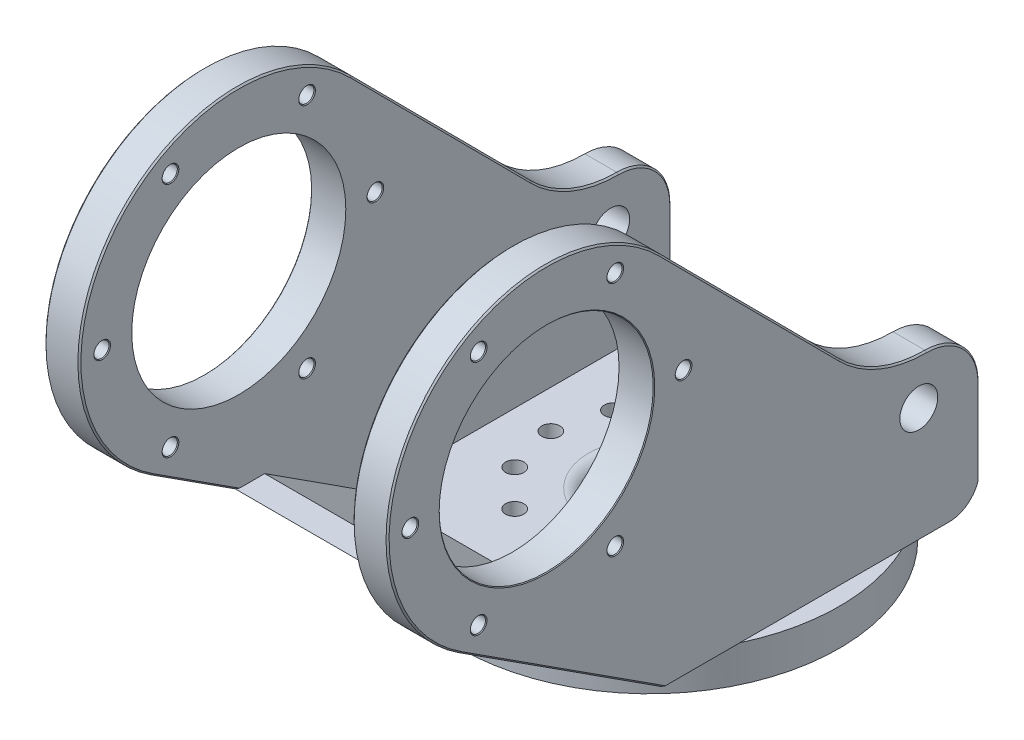
SolidWorks part; units mm, degrees
ref_plane "前视基准面" through (0, 0, 0) normal (0, 0, 1) x (1, 0, 0)
ref_plane "上视基准面" through (0, 0, 0) normal (0, 1, 0) x (1, 0, 0)
ref_plane "右视基准面" through (0, 0, 0) normal (1, 0, 0) x (0, 0, -1)
other "Configuration Table"
sketch "草图1" plane through (0, 0, 0) normal (0, 1, 0) x (1, 0, 0)
  circle A0 centre (0, 0) radius 125
  dimension "D1" = 250
extrude "凸台-拉伸1" add sketch "草图1" along normal mid plane 29
sketch "草图2" plane through (0, 0, 0) normal (1, 0, 0) x (0, 0, -1)
  line L0 (0, -14.5) -> (55, -14.5)
  line L1 (-125, -14.5) -> (125, -14.5) construction
  line L2 (55, -14.5) -> (55, -10.5)
  line L3 (55, -10.5) -> (30, -10.5)
  line L4 (30, -10.5) -> (30, 4.5)
  line L6 (125, 14.5) -> (-125, 14.5) construction
  line L7 (0, -14.5) -> (0, 14.5)
  line L8 (0, 14.5) -> (40, 14.5)
  arc A0 (30, 4.5) -> (40, 14.5) centre (40, 4.5) cw
  dimension "D3" = 10
  dimension "D1" = 55
  dimension "D2" = 30
  dimension "D4" = 4
revolve "切除-旋转1" cut sketch "草图2" angle 360 about L7
sketch "草图3" plane through (0, 14.5, 0) normal (0, 1, 0) x (1, 0, 0)
  circle A0 centre (0, 0) radius 65 construction
  circle A1 centre (0, 65) radius 6
  circle A2 centre (32.5, 56.2917) radius 6
  circle A3 centre (56.2917, 32.5) radius 6
  circle A4 centre (65, 0) radius 6
  circle A5 centre (56.2917, -32.5) radius 6
  circle A6 centre (32.5, -56.2917) radius 6
  circle A7 centre (0, -65) radius 6
  circle A8 centre (-32.5, -56.2917) radius 6
  circle A9 centre (-56.2917, -32.5) radius 6
  circle A10 centre (-65, 0) radius 6
  circle A11 centre (-56.2917, 32.5) radius 6
  circle A12 centre (-32.5, 56.2917) radius 6
  point P29 (0, 0)
  dimension "D1" = 130
  dimension "D2" = 12
  dimension "D3" = 12
extrude "切除-拉伸1" cut sketch "草图3" against normal blind 29
sketch "草图4" plane through (0, 14.5, 0) normal (0, 1, 0) x (1, 0, 0)
  line L1 (-90, 125) -> (90, 125)
  line L2 (-90, 125) -> (-90, -125)
  line L3 (-90, -125) -> (90, -125)
  line L4 (90, 125) -> (90, -125)
  line L5 (-90, 125) -> (90, -125) construction
  line L6 (-90, -125) -> (90, 125) construction
  circle A0 centre (0, 0) radius 125 construction
  point P0 (0, 0)
  dimension "D1" = 180
extrude "切除-拉伸2" cut sketch "草图4" against normal blind 5 flip side to cut
sketch "草图5" plane through (-90, 0, 0) normal (-1, 0, 0) x (0, 0, 1)
  line L0 (-104.4, 9.5) -> (104.4, 9.5)
  line L1 (104.4, 9.5) -> (237.47, 95.3235)
  line L2 (106.086, 257.581) -> (-12.658, 138.1055)
  line L3 (-104.4, 79.5) -> (-104.4, 9.5)
  arc A0 (237.47, 95.3235) -> (106.086, 257.581) centre (180.5598, 183.5632) ccw
  arc A1 (-12.658, 138.1055) -> (-69.4, 114.5) centre (-69.4, 194.5) cw
  arc A2 (-69.4, 114.5) -> (-104.4, 79.5) centre (-69.4, 79.5) ccw
  circle A3 centre (180.5598, 183.5632) radius 90 construction
  circle A4 centre (270.5598, 183.5632) radius 5
  circle A5 centre (225.5598, 105.6209) radius 5
  circle A6 centre (135.5598, 105.6209) radius 5
  circle A7 centre (90.5598, 183.5632) radius 5
  circle A8 centre (135.5598, 261.5054) radius 5
  circle A9 centre (225.5598, 261.5054) radius 5
  circle A10 centre (180.5598, 183.5632) radius 70.5
  circle A11 centre (-64.4, 84.5) radius 12.5
  point P15 (0, 9.5)
  point P31 (180.5598, 183.5632)
  dimension "D4" = 105
  dimension "D5" = 80
  dimension "D6" = 35
  dimension "D9" = 180
  dimension "D10" = 10
  dimension "D12" = 141
  dimension "D15" = 25
  dimension "D1" = 208.8
  dimension "D2" = 32.82
  dimension "D3" = 133.07
  dimension "D7" = 185
  dimension "D8" = 105
  dimension "D13" = 40
  dimension "D14" = 30
  dimension "D11" = 6
extrude "凸台-拉伸2" add sketch "草图5" along normal blind 23
mirror "镜向1" about plane through (0, 0, 0) normal (1, 0, 0) of "凸台-拉伸2"
sketch "草图6" plane through (-90, 0, 0) normal (1, 0, 0) x (0, 0, -1)
  line L0 (-112.1525, 14.5) -> (-93.7024, 14.5)
  line L1 (-104.4, 9.5) -> (-237.47, 95.3235) construction
  line L2 (-86.7468, 14.5) -> (-125, 14.5) construction
  line L3 (-93.7024, 14.5) -> (-163.4752, 59.5)
  line L4 (-163.4752, 59.5) -> (-181.9254, 59.5)
  line L5 (-181.9254, 59.5) -> (-112.1525, 14.5)
  dimension "D1" = 10
  dimension "D2" = 45
extrude "凸台-拉伸3" add sketch "草图6" along normal up to next
chamfer "倒角1" distance 1 angle 45 25 edges at (0, -10.5, -30) (90, 249.6389, 262.1625) (90, 44.5, -104.4) (90, 197.8432, 46.714) (90, 104.2487, -94.1487) (90, 120.6367, -38.6719) (113, 52.4118, 170.935) (113, 249.6389, 262.1625) (113, 44.5, -104.4) (113, 197.8432, 46.714) (113, 104.2487, -94.1487) (113, 120.6367, -38.6719) (-113, 52.4118, 170.935) (-113, 249.6389, 262.1625) (-113, 197.8432, 46.714) (-113, 120.6367, -38.6719) (-113, 104.2487, -94.1487) (-113, 44.5, -104.4) (-90, 249.6389, 262.1625) (-90, 44.5, -104.4) (-90, 197.8432, 46.714) (-90, 104.2487, -94.1487) (-90, 120.6367, -38.6719) (90, 77.4118, 209.6977) (-90, 77.4118, 209.6977)
chamfer "倒角2" distance 0.5 angle 45 26 edges at (-90, 105.6209, 230.5598) (-113, 105.6209, 230.5598) (-90, 105.6209, 140.5598) (-113, 105.6209, 140.5598) (-90, 183.5632, 95.5598) (-113, 183.5632, 95.5598) (-90, 261.5054, 140.5598) (-113, 261.5054, 140.5598) (-90, 261.5054, 230.5598) (-113, 261.5054, 230.5598) (-90, 183.5632, 275.5598) (-113, 183.5632, 275.5598) (90, 183.5632, 95.5598) (113, 183.5632, 95.5598) (90, 261.5054, 140.5598) (113, 261.5054, 140.5598) (90, 261.5054, 230.5598) (113, 261.5054, 230.5598) (90, 183.5632, 275.5598) (113, 183.5632, 275.5598) (90, 105.6209, 140.5598) (113, 105.6209, 140.5598) (90, 105.6209, 230.5598) (113, 105.6209, 230.5598) (-113, 183.5632, 251.0598) (113, 183.5632, 251.0598)
fillet "圆角1" radius 20 2 edges at (101.5, 9.5, -104.4) (-101.5, 9.5, -104.4)
